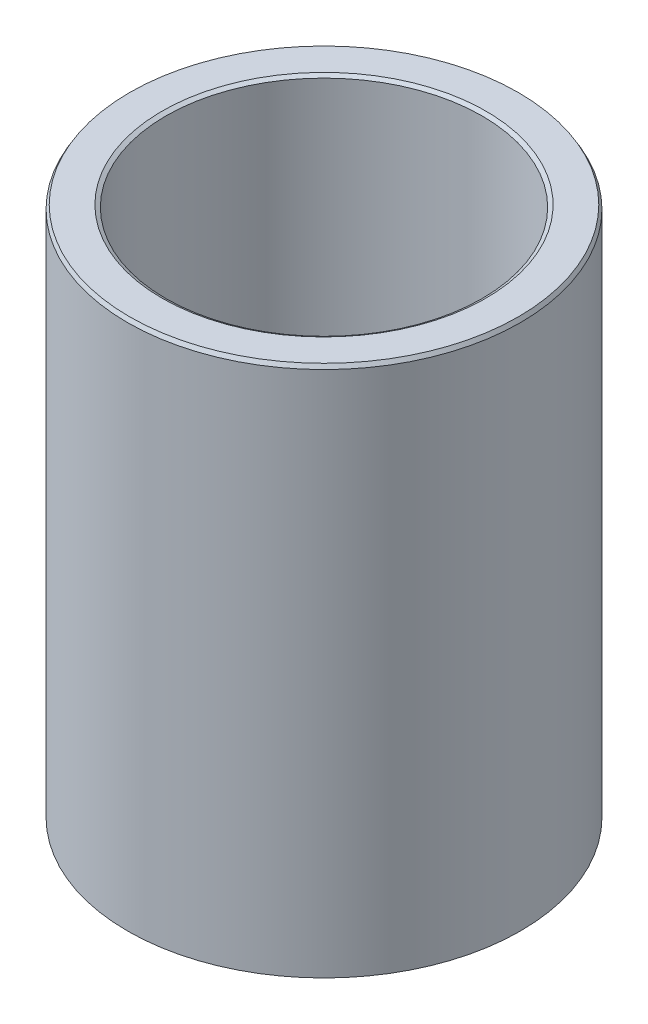
SolidWorks part; units mm, degrees
ref_plane "Front Plane" through (0, 0, 0) normal (0, 0, 1) x (1, 0, 0)
ref_plane "Top Plane" through (0, 0, 0) normal (0, 1, 0) x (1, 0, 0)
ref_plane "Right Plane" through (0, 0, 0) normal (1, 0, 0) x (0, 0, -1)
sketch "Sketch1" plane through (0, 0, 0) normal (0, 1, 0) x (1, 0, 0)
  circle A0 centre (0, 0) radius 15
  dimension "SLEEVE_OD" = 30
extrude "Boss-Extrude1" add sketch "Sketch1" along normal blind 40.6776
sketch "Sketch2" plane through (0, 0, 0) normal (0, 1, 0) x (1, 0, 0)
  circle A0 centre (0, 0) radius 12.071
  dimension "BORE_D" = 24.1419
extrude "Cut-Extrude1" cut sketch "Sketch2" along normal through all
chamfer "Chamfer1" distance 0.2943 angle 30 4 edges at (0, 40.6776, 12.071) (0, 0, 12.071) (0, 0, 15) (0, 40.6776, 15) first distance on face at (0, 40.6776, 12.071) first distance on face at (0, 0, 12.071) first distance on face at (0, 40.6776, 15)
